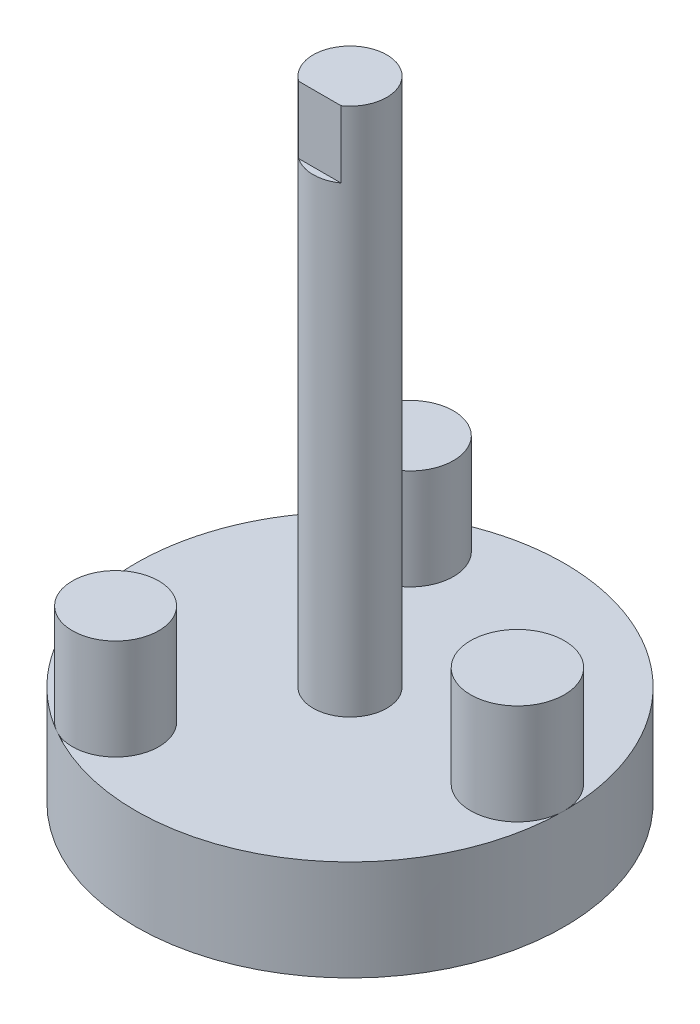
SolidWorks part; units mm, degrees
ref_plane "Front Plane" through (0, 0, 0) normal (0, 0, 1) x (1, 0, 0)
ref_plane "Top Plane" through (0, 0, 0) normal (0, 1, 0) x (1, 0, 0)
ref_plane "Right Plane" through (0, 0, 0) normal (1, 0, 0) x (0, 0, -1)
sketch "Sketch1" plane through (0, 0, 0) normal (0, 1, 0) x (1, 0, 0)
  circle A0 centre (0, 0) radius 32
  dimension "D1" = 64
extrude "Boss-Extrude1" add sketch "Sketch1" along normal blind 15
sketch "Sketch2" plane through (0, 15, 0) normal (0, 1, 0) x (1, 0, 0)
  circle A4 centre (25, 0) radius 7
  circle A5 centre (-13, 22) radius 6.4461
  circle A6 centre (-13, -22) radius 6.4461
extrude "Boss-Extrude2" add sketch "Sketch2" along normal blind 15
sketch "Sketch3" plane through (0, 15, 0) normal (0, 1, 0) x (1, 0, 0)
  circle A0 centre (0, 0) radius 5.5
  dimension "D1" = 11
extrude "Boss-Extrude3" add sketch "Sketch3" along normal blind 79
sketch "Sketch4" plane through (0, 0, 0) normal (1, 0, 0) x (0, 0, -1)
  line L1 (5.5, 94) -> (-5.5, 94) construction
  line L2 (-4.5, 94) -> (-4.5, 84)
  line L3 (-4.5, 84) -> (-8.7576, 84)
  line L4 (-8.7576, 84) -> (-8.7576, 94)
  line L5 (-8.7576, 94) -> (-4.5, 94)
  dimension "D2" = 10
extrude "Cut-Extrude1" cut sketch "Sketch4" against normal blind 79 and the other way blind 79
